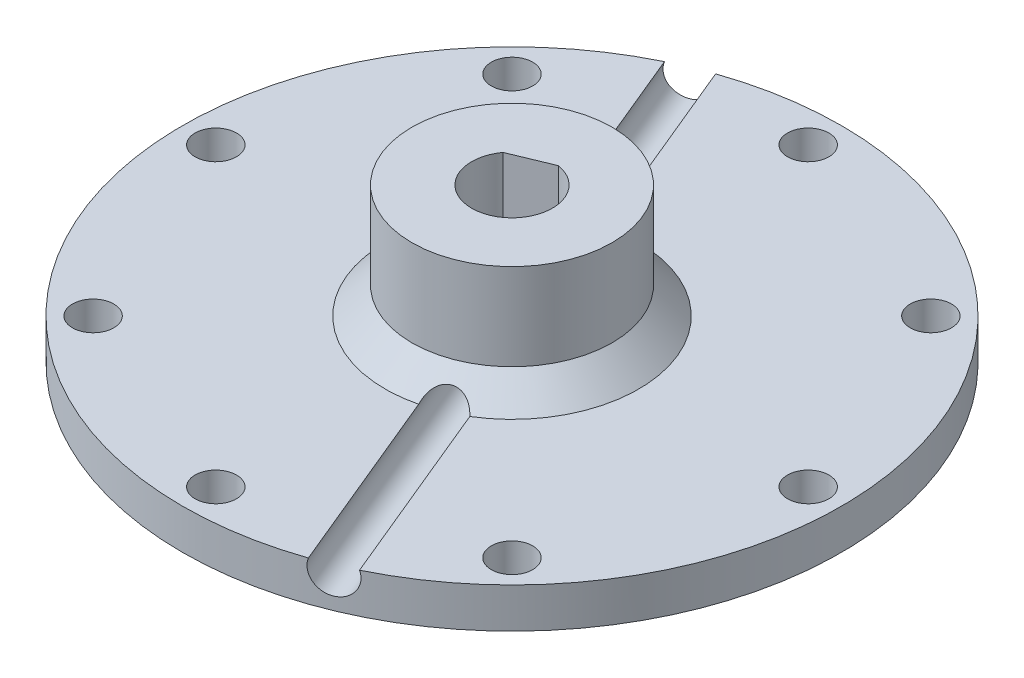
SolidWorks part; units mm, degrees
ref_plane "前视基准面" through (0, 0, 0) normal (0, 0, 1) x (1, 0, 0)
ref_plane "上视基准面" through (0, 0, 0) normal (0, 1, 0) x (1, 0, 0)
ref_plane "右视基准面" through (0, 0, 0) normal (1, 0, 0) x (0, 0, -1)
other "Configuration Table"
sketch "草图1" plane through (0, 0, 0) normal (0, 1, 0) x (1, 0, 0)
  line L5 (0, 39.1969) -> (0, 0) construction
  line L6 (-11.5558, 27.8983) -> (0, 0) construction
  line L7 (-27.7164, 27.7164) -> (0, 39.1969) construction
  line L8 (-11.5558, 27.8983) -> (-13.8582, 33.4566) construction
  line L9 (-22.2263, 37.9802) -> (-16.8687, 25.0459)
  line L10 (-11.1397, 42.5724) -> (-5.7822, 29.6381)
  line L11 (-22.2263, 37.9802) -> (-11.1397, 42.5724)
  line L20 (-19.6962, 0) -> (-24.6962, 0) construction
  line L21 (0, 19.6962) -> (-13.9273, 13.9273) construction
  line L22 (-13.9273, 13.9273) -> (-19.6962, 0) construction
  line L23 (-19.6962, 0) -> (-13.9273, -13.9273) construction
  line L24 (-13.9273, -13.9273) -> (0, -19.6962) construction
  line L25 (0, -19.6962) -> (13.9273, -13.9273) construction
  line L26 (13.9273, -13.9273) -> (19.6962, 0) construction
  line L27 (19.6962, 0) -> (13.9273, 13.9273) construction
  line L28 (13.9273, 13.9273) -> (0, 19.6962) construction
  line L29 (-2.452, 1.7715) -> (0.4812, 2.9865)
  line L30 (0, 0) -> (1.1576, -2.7947) construction
  circle A1 centre (0, 0) radius 30.1969 construction
  circle A2 centre (0, 39.1969) radius 9 construction
  circle A3 centre (27.7164, 27.7164) radius 9 construction
  circle A4 centre (39.1969, 0) radius 9 construction
  circle A5 centre (27.7164, -27.7164) radius 9 construction
  circle A6 centre (0, -39.1969) radius 9 construction
  circle A7 centre (-27.7164, -27.7164) radius 9 construction
  circle A8 centre (-39.1969, 0) radius 9 construction
  circle A9 centre (-27.7164, 27.7164) radius 9 construction
  circle A10 centre (0, 0) radius 18.1969 construction
  circle A11 centre (0, 0) radius 24.6962
  circle A12 centre (-22.1962, 0) radius 1.55
  circle A13 centre (-15.6951, 15.6951) radius 1.55
  circle A14 centre (0, 22.1962) radius 1.55
  circle A15 centre (15.6951, 15.6951) radius 1.55
  circle A16 centre (22.1962, 0) radius 1.55
  circle A17 centre (15.6951, -15.6951) radius 1.55
  circle A18 centre (0, -22.1962) radius 1.55
  circle A19 centre (-15.6951, -15.6951) radius 1.55
  circle A20 centre (0, 0) radius 3.025
  circle A21 centre (0, 0) radius 7.5
  point P21 (0, 0)
  point P55 (0, 0)
  dimension "D2" = 18
  dimension "D6" = 5
  dimension "D7" = 3.1
  dimension "D9" = 6.05
  dimension "D10" = 15
  dimension "D3" = 12
  dimension "D4" = 14
  dimension "D5" = 12
  dimension "D11" = 5.6
  dimension "D1" = 8
  dimension "D8" = 8
extrude "凸台-拉伸1" add sketch "草图1" along normal blind 3 contours A11 A20 A19 A18 A17 A16 A15 A14 A13 A12 region at (-23.9977, 0, 0)
extrude "凸台-拉伸2" add sketch "草图1<4>" along normal blind 11.5 contours A21 A20 | L29 A20 region at (-1.0548, 0, -2.5464) region at (-7.2879, 0, 0)
sketch "草图1<4>" plane through (0, 0, 0) normal (0, 1, 0) x (1, 0, 0) same geometry as "草图1"
chamfer "倒角2" distance 2 angle 45 1 edges at (0, 3, 7.5)
sketch "草图5" plane through (-0.9854, 0, -2.379) normal (0.3827, 0, 0.9239) x (0.9239, 0, -0.3827)
  line L0 (0, 2.5) -> (0, 0) construction
  circle A0 centre (0, 2.5) radius 1.55
  dimension "D1" = 3.1
  dimension "D2" = 2.5
extrude "切除-拉伸2" cut sketch "草图5" against normal through all both and the other way through all
